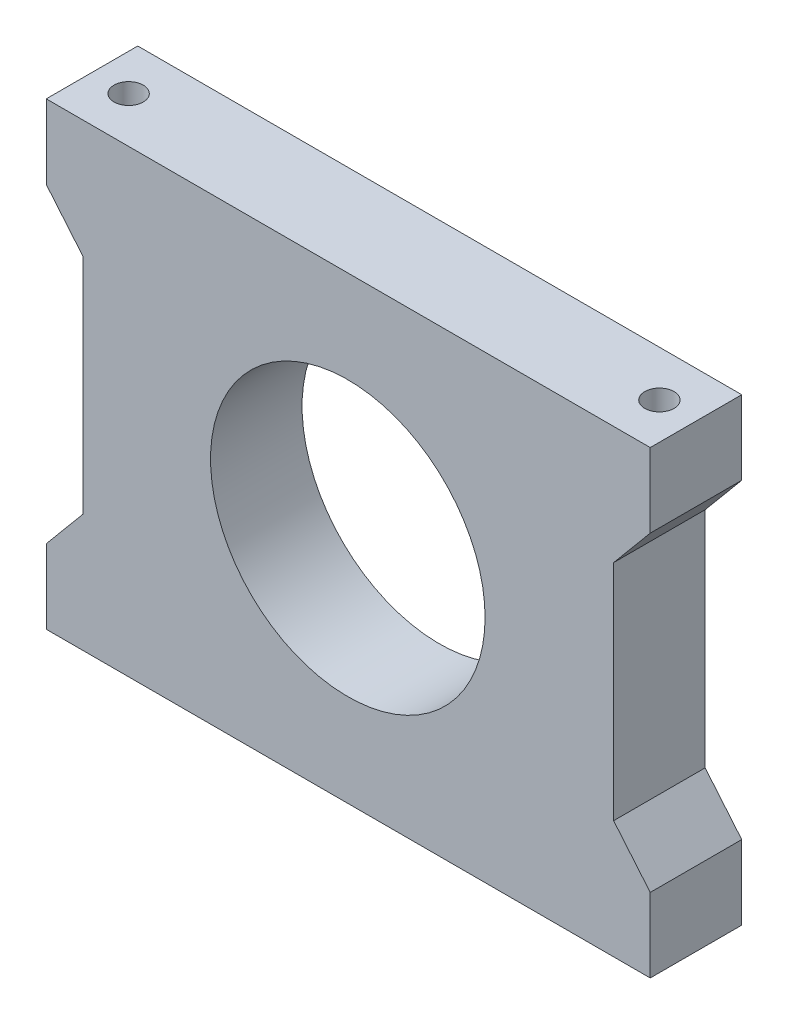
SolidWorks part; units mm, degrees
material "3.0205 (EN-AW 1200)"
ref_plane "Płaszczyzna przednia" through (0, 0, 0) normal (0, 0, 1) x (1, 0, 0)
ref_plane "Płaszczyzna górna" through (0, 0, 0) normal (0, 1, 0) x (1, 0, 0)
ref_plane "Płaszczyzna prawa" through (0, 0, 0) normal (1, 0, 0) x (0, 0, -1)
sketch "Szkic1" plane through (0, 0, 0) normal (0, 0, 1) x (1, 0, 0)
  line L0 (0, 0) -> (66, 0)
  line L1 (0, 0) -> (0, 50.2) construction
  line L3 (66, 50.2) -> (0, 50.2)
  line L4 (66, 0) -> (66, 8.1)
  line L5 (66, 8.1) -> (62, 12.8869)
  line L6 (62, 12.8869) -> (62, 37.3131)
  line L7 (0, 25.1) -> (37.9059, 25.1) construction
  line L8 (33, 1.7581) -> (33, 11.1868) construction
  line L9 (32.9524, 8.1) -> (50032.9524, 8.1) construction
  line L10 (32.9524, 10.1) -> (33, 8.1) construction
  line L11 (66, 42.1) -> (62, 37.3131)
  line L12 (66, 50.2) -> (66, 42.1)
  line L13 (0, 50.2) -> (0, 42.1)
  line L14 (0, 42.1) -> (4, 37.3131)
  line L15 (4, 12.8869) -> (4, 37.3131)
  line L16 (0, 8.1) -> (4, 12.8869)
  line L17 (0, 0) -> (0, 8.1)
  circle A1 centre (32.9524, 25.1) radius 15
  point P19 (62, 25.1)
  dimension "D3" = 30
  dimension "D2" = 66
  dimension "D4" = 4
  dimension "D5" = 2
extrude "Dodanie-wyciągnięcie1" add sketch "Szkic1" along normal blind 10
sketch "Szkic2" plane through (0, 50.2, 0) normal (0, 1, 0) x (1, 0, 0)
  line L0 (33, 0) -> (33, -10) construction
  line L1 (66, 0) -> (0, 0) construction
  line L2 (66, -10) -> (0, -10) construction
  line L3 (4, -5) -> (62, -5) construction
  circle A0 centre (4, -5) radius 1.6
  circle A1 centre (62, -5) radius 1.6
  point P9 (33, -5)
  dimension "D2" = 3.2
  dimension "D1" = 58
extrude "Wytnij-wyciągnięcie1" cut sketch "Szkic2" against normal blind 10
ref_plane "Płaszczyzna2" through (0, 25.1, 0) normal (0, 1, 0) x (1, 0, 0)
mirror "Lustro1" about plane through (0, 25.1, 0) normal (0, 1, 0) of "Wytnij-wyciągnięcie1"
